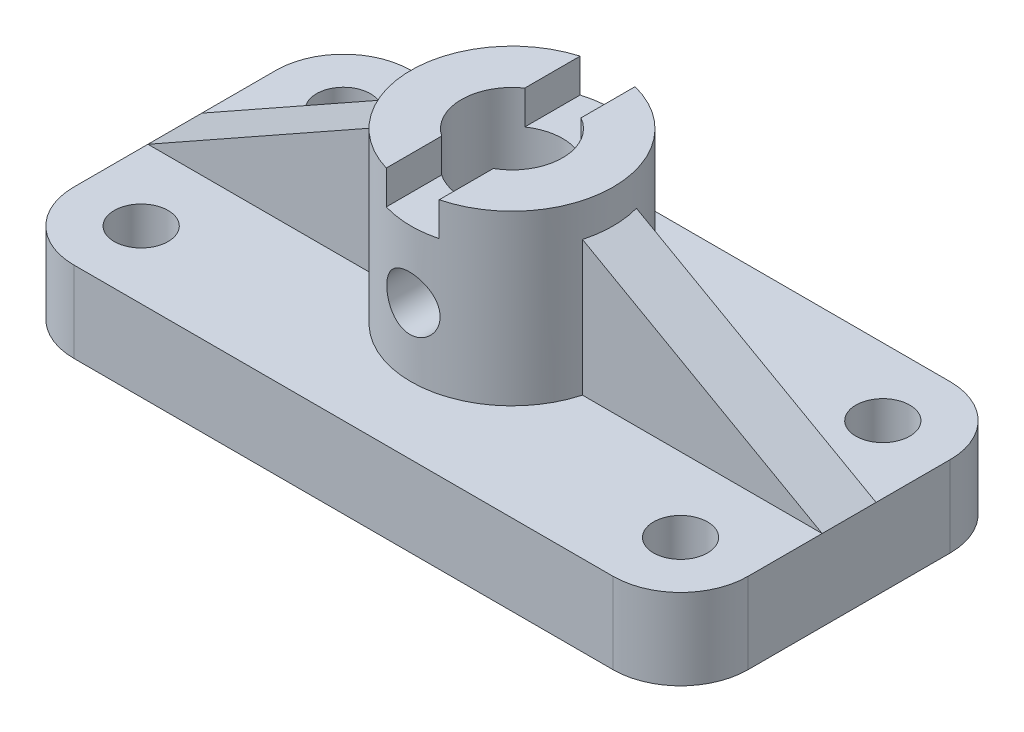
SolidWorks part; units mm, degrees
ref_plane "前视基准面" through (0, 0, 0) normal (0, 0, 1) x (1, 0, 0)
ref_plane "上视基准面" through (0, 0, 0) normal (0, 1, 0) x (1, 0, 0)
ref_plane "右视基准面" through (0, 0, 0) normal (1, 0, 0) x (0, 0, -1)
other "Configuration Table"
sketch "草图1" plane through (0, 0, 0) normal (0, 1, 0) x (1, 0, 0)
  line L0 (-50, 15) -> (-50, 25)
  line L1 (-50, -25) -> (50, -25)
  line L2 (-50, -25) -> (-50, 25)
  line L3 (-50, 25) -> (50, 25)
  line L4 (50, -25) -> (50, 25)
  line L5 (0, 25) -> (0, -25) construction
  line L6 (-50, 0) -> (50, 0) construction
  line L7 (-50, -15) -> (-50, -25)
  line L8 (40, -25) -> (50, -25)
  line L9 (40, 25) -> (50, 25)
  line L10 (50, 15) -> (50, 25)
  circle A0 centre (-40, 15) radius 4
  circle A1 centre (-40, -15) radius 4
  circle A2 centre (40, -15) radius 4
  circle A3 centre (40, 15) radius 4
  arc A4 (-50, 15) -> (-40, 25) centre (-40, 15) cw
  arc A5 (50, 15) -> (40, 25) centre (40, 15) ccw
  arc A6 (-50, -15) -> (-40, -25) centre (-40, -15) ccw
  arc A7 (50, -15) -> (40, -25) centre (40, -15) cw
  point P0 (0, 0)
  dimension "D3" = 8
  dimension "D1" = 100
  dimension "D2" = 50
  dimension "D4" = 30
  dimension "D5" = 80
  dimension "D6" = 10
  dimension "D7" = 80
extrude "凸台-拉伸1" add sketch "草图1" along normal blind 12 contours A7 L4 A5 L3 A4 L2 A6 L1 A2 A1 A0 A3
sketch "草图3" plane through (0, 12, 0) normal (0, 1, 0) x (1, 0, 0)
  line L0 (-50, -4) -> (-14.4568, -4)
  line L1 (-50, -15) -> (-50, 15) construction
  line L2 (-50, 4) -> (-14.4568, 4)
  line L3 (-50, 4) -> (-50, -4)
  line L4 (0, 0) -> (-57.0715, 0) construction
  circle A0 centre (0, 0) radius 15
  arc A1 (-14.4568, 4) -> (-14.4383, -4.0662) centre (0, 0) cw
  arc A2 (-14.4568, 4) -> (-14.4568, -4) centre (0, 0) ccw
  dimension "D2" = 30
  dimension "D1" = 8
  dimension "D3" = 4
extrude "凸台-拉伸3" add sketch "草图3" along normal blind 25
sketch "草图6" plane through (0, 0, 4) normal (0, 0, 1) x (1, 0, 0)
  line L1 (-14.4568, 37) -> (-14.4568, 12) construction
  line L2 (-14.4568, 32) -> (-50, 12)
  line L3 (-3.7284, 37) -> (-3.7284, 32)
  line L4 (15, 37) -> (-14.4568, 37) construction
  line L5 (-3.7284, 32) -> (4.2716, 32)
  line L6 (4.2716, 32) -> (4.2716, 37)
  line L11 (0, 0) -> (0.2716, 37) construction
  line L12 (-40, 0) -> (40, 0) construction
  line L13 (-3.7284, 37) -> (4.2716, 37)
  line L14 (-14.4568, 12) -> (14.8484, 12) construction
  line L15 (-40, 12) -> (40, 12) construction
  line L16 (-14.4568, 32) -> (-50, 32)
  line L17 (-50, 37) -> (-50, 12) construction
  line L18 (-50, 32) -> (-50, 12)
  circle A0 centre (0.1615, 22) radius 4
  dimension "D3" = 8
  dimension "D1" = 20
  dimension "D2" = 8
  dimension "D4" = 10
sketch "草图7" plane through (0, 37, 0) normal (0, 1, 0) x (1, 0, 0)
  line L0 (-14.4568, 4) -> (-50, 4)
  line L1 (-50, 4) -> (-14.4568, 4) construction
  line L2 (-50, 4) -> (-50, -4) construction
  line L3 (-50, 4) -> (-50, -4)
  line L4 (-50, -4) -> (-14.4568, -4)
  arc A0 (-14.4568, 4) -> (-14.4568, -4) centre (0, 0) ccw
  arc A1 (-14.4568, -4) -> (-14.4568, 4) centre (0, 0) ccw construction
extrude "切除-拉伸2" cut sketch "草图7" against normal blind 5 contours A0 L4 L3 L0
extrude "切除-拉伸3" cut sketch "草图6" against normal through all and the other way through all
mirror "镜向3" about plane through (0, 0, 0) normal (1, 0, 0) of "凸台-拉伸3", "切除-拉伸2", "切除-拉伸3"
sketch "草图10" plane through (0, 37, 0) normal (0, 1, 0) x (1, 0, 0)
  circle A0 centre (0, 0) radius 7.5
  dimension "D1" = 15
extrude "切除-拉伸4" cut sketch "草图10" against normal through all
